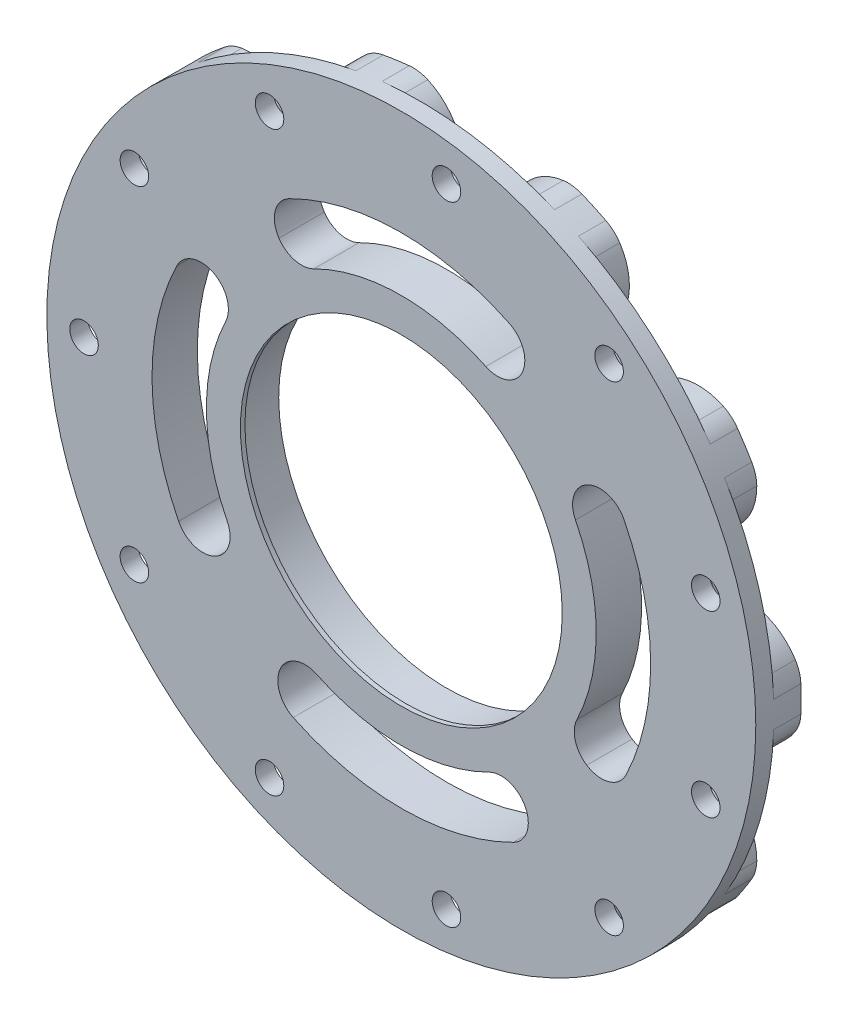
SolidWorks part; units mm, degrees
material "ABS"
ref_plane "Front Plane" through (0, 0, 0) normal (0, 0, 1) x (1, 0, 0)
ref_plane "Top Plane" through (0, 0, 0) normal (0, 1, 0) x (1, 0, 0)
ref_plane "Right Plane" through (0, 0, 0) normal (1, 0, 0) x (0, 0, -1)
ref_plane "Plane1" through (0, 0, 15) normal (0, 0, 1) x (1, 0, 0)
sketch "Sketch1" plane through (0, 0, 15) normal (0, 0, 1) x (1, 0, 0)
  circle A0 centre (0, 0) radius 39.1
  circle A1 centre (0, 0) radius 33 construction
  circle A2 centre (33, 0) radius 2.525
  circle A3 centre (27.7614, -17.8411) radius 2.525
  circle A4 centre (13.7087, -30.0179) radius 2.525
  circle A5 centre (-4.6964, -32.6641) radius 2.525
  circle A6 centre (-21.6104, -24.9397) radius 2.525
  circle A7 centre (-31.6633, -9.2972) radius 2.525
  circle A8 centre (-31.6633, 9.2972) radius 2.525
  circle A9 centre (-21.6104, 24.9397) radius 2.525
  circle A10 centre (-4.6964, 32.6641) radius 2.525
  circle A11 centre (13.7087, 30.0179) radius 2.525
  circle A12 centre (27.7614, 17.8411) radius 2.525
  circle A13 centre (0, 0) radius 16.025
  point P28 (0, 0)
extrude "Boss-Extrude1" add sketch "Sketch1" along normal blind 5
sketch "Sketch2" plane through (0, 0, 15) normal (0, 0, -1) x (-1, 0, 0)
  circle A0 centre (0, 0) radius 18.525
  dimension "D1" = 37.05
extrude "Cut-Extrude1" cut sketch "Sketch2" against normal blind 4.5
sketch "Sketch3" plane through (0, 0, 20) normal (0, 0, 1) x (1, 0, 0)
  circle A1 centre (-4.6964, 32.6641) radius 2.55
  circle A2 centre (13.7087, 30.0179) radius 2.55
  circle A4 centre (27.7614, 17.8411) radius 2.55
  circle A6 centre (33, 0) radius 2.55
  circle A8 centre (27.7614, -17.8411) radius 2.55
  circle A10 centre (13.7087, -30.0179) radius 2.55
  circle A12 centre (-4.6964, -32.6641) radius 2.55
  circle A14 centre (-21.6104, -24.9397) radius 2.55
  circle A16 centre (-31.6633, -9.2972) radius 2.55
  circle A18 centre (-31.6633, 9.2972) radius 2.55
  circle A20 centre (-21.6104, 24.9397) radius 2.55
  point P36 (0, 0)
  dimension "D1" = 5.1
  dimension "D3" = 11
extrude "Boss-Extrude2" add sketch "Sketch3" against normal blind 4
chamfer "Chamfer3" distance 0.5 angle 45 11 edges at (35.525, 0, 15) (30.2864, -17.8411, 15) (16.2337, -30.0179, 15) (-2.1714, -32.6641, 15) (-19.0854, -24.9397, 15) (-29.1383, -9.2972, 15) (-29.1383, 9.2972, 15) (-19.0854, 24.9397, 15) (-2.1714, 32.6641, 15) (16.2337, 30.0179, 15) (30.2864, 17.8411, 15)
sketch "Sketch4" plane through (0, 0, 15) normal (0, 0, -1) x (-1, 0, 0)
  arc A0 (-7.5917, 32.0635) -> (-19.2605, 26.7345) centre (-13.7087, 30.0179) ccw
  circle A1 centre (0, 0) radius 39.1
  arc A2 (10.9483, 31.0779) -> (-1.7492, 32.9035) centre (4.6964, 32.6641) ccw
  arc A3 (26.0123, 20.2253) -> (16.3175, 28.6259) centre (21.6104, 24.9397) ccw
  arc A4 (32.8176, 2.9513) -> (29.2035, 15.2597) centre (31.6633, 9.2972) ccw
  arc A5 (29.2035, -15.2597) -> (32.8176, -2.9513) centre (31.6633, -9.2972) ccw
  arc A6 (16.3175, -28.6259) -> (26.0123, -20.2253) centre (21.6104, -24.9397) ccw
  arc A7 (-1.7492, -32.9035) -> (10.9483, -31.0779) centre (4.6964, -32.6641) ccw
  arc A8 (-19.2605, -26.7345) -> (-7.5917, -32.0635) centre (-13.7087, -30.0179) ccw
  arc A9 (-30.6567, -12.0775) -> (-23.7214, -22.8692) centre (-27.7614, -17.8411) ccw
  arc A10 (-32.3197, 6.414) -> (-32.3197, -6.414) centre (-33, 0) ccw
  arc A11 (-23.7214, 22.8692) -> (-30.6567, 12.0775) centre (-27.7614, 17.8411) ccw
  arc A12 (-32.3197, -6.414) -> (-30.6567, -12.0775) centre (0, 0) ccw
  arc A13 (-30.6567, 12.0775) -> (-32.3197, 6.414) centre (0, 0) ccw
  arc A14 (-19.2605, 26.7345) -> (-23.7214, 22.8692) centre (0, 0) ccw
  arc A15 (-1.7492, 32.9035) -> (-7.5917, 32.0635) centre (0, 0) ccw
  arc A16 (16.3175, 28.6259) -> (10.9483, 31.0779) centre (0, 0) ccw
  arc A17 (29.2035, 15.2597) -> (26.0123, 20.2253) centre (0, 0) ccw
  arc A18 (32.8176, -2.9513) -> (32.8176, 2.9513) centre (0, 0) ccw
  arc A19 (26.0123, -20.2253) -> (29.2035, -15.2597) centre (0, 0) ccw
  arc A20 (10.9483, -31.0779) -> (16.3175, -28.6259) centre (0, 0) ccw
  arc A21 (-7.5917, -32.0635) -> (-1.7492, -32.9035) centre (0, 0) ccw
  arc A22 (-23.7214, -22.8692) -> (-19.2605, -26.7345) centre (0, 0) ccw
  point P28 (0, 0)
  circle M36 centre (0, 0) radius 39.1
  dimension "D1" = 12.9
  dimension "D2" = 78.2
  dimension "D4" = 65.9
  dimension "D3" = 11
extrude "Cut-Extrude2" cut sketch "Sketch4" against normal blind 3 contours A15 A2 A0 M36 | A16 A3 A2 M36 | A17 A4 A3 M36 | A18 A5 A4 M36 | A19 A6 A5 M36 | A20 A7 A6 M36 | A21 A8 A7 M36 | A22 A9 A8 M36 | A12 A10 A9 M36 | A13 A11 A10 M36 | A14 A0 A11 M36 region at (5.1877, 36.0815, 15) region at (23.8713, 27.549, 15) region at (-15.1429, 33.1584, 15) region at (34.9759, 10.2699, 15) region at (-30.6658, 19.7077, 15) region at (34.9759, -10.2699, 15) region at (-36.4525, 0, 15) region at (23.8713, -27.549, 15) region at (5.1877, -36.0815, 15) region at (-30.6658, -19.7077, 15) region at (-15.1429, -33.1584, 15)
fillet "Fillet1" radius 4 22 edges at (-38.0948, -8.809, 16.5) (-36.8099, -13.185, 16.5) (-27.2848, -28.0062, 16.5) (-23.8381, -30.9928, 16.5) (-7.8122, -38.3116, 16.5) (-3.2979, -38.9607, 16.5) (14.1408, -36.4534, 16.5) (18.2894, -34.5588, 16.5) (31.6042, -23.0214, 16.5) (34.0699, -19.1847, 16.5) (39.0334, 2.2804, 16.5) (39.0334, -2.2804, 16.5) (34.0699, 19.1847, 16.5) (31.6042, 23.0214, 16.5) (14.1408, 36.4534, 16.5) (18.2894, 34.5588, 16.5) (-3.2979, 38.9607, 16.5) (-7.8122, 38.3116, 16.5) (-38.0948, 8.809, 16.5) (-36.8099, 13.185, 16.5) (-27.2848, 28.0062, 16.5) (-23.8381, 30.9928, 16.5)
sketch "Sketch5" plane through (0, 0, 20) normal (0, 0, 1) x (1, 0, 0)
  circle A0 centre (0, 0) radius 17.75
  dimension "D1" = 35.5
extrude "Cut-Extrude3" cut sketch "Sketch5" against normal blind 10
chamfer "Chamfer5" [suppressed] distance 0.5 angle 45
sketch "Sketch6" plane through (0, 0, 15) normal (0, 0, -1) x (-1, 0, 0)
  line L0 (0, 0) -> (-27.4458, 18.3229)
  line L1 (0, 0) -> (-27.7614, -17.8411)
  line L2 (0, 0) -> (18.3229, 27.4458)
  line L3 (0, 0) -> (-17.8411, 27.7614)
  line L4 (0, 0) -> (27.4458, -18.3229)
  line L5 (0, 0) -> (27.7614, 17.8411)
  line L6 (0, 0) -> (-18.3229, -27.4458)
  line L7 (0, 0) -> (17.8411, -27.7614)
  line L8 (0, 0) -> (-33, 0) construction
  arc A0 (-18.087, -11.6238) -> (-17.8813, 11.9377) centre (0, 0) cw
  arc A1 (-23.1345, -14.8676) -> (-22.8715, 15.2691) centre (0, 0) cw
  arc A2 (-14.8676, 23.1345) -> (15.2691, 22.8715) centre (0, 0) cw
  arc A3 (-11.6238, 18.087) -> (11.9377, 17.8813) centre (0, 0) cw
  arc A4 (23.1345, 14.8676) -> (22.8715, -15.2691) centre (0, 0) cw
  arc A5 (18.087, 11.6238) -> (17.8813, -11.9377) centre (0, 0) cw
  arc A6 (14.8676, -23.1345) -> (-15.2691, -22.8715) centre (0, 0) cw
  arc A7 (11.6238, -18.087) -> (-11.9377, -17.8813) centre (0, 0) cw
  point P10 (-33, 0)
  point P31 (0, 0)
  dimension "D1" = 21.5
  dimension "D2" = 27.5
  dimension "D4" = 33.727
  dimension "D5" = 32.727
  dimension "D3" = 4
extrude "Cut-Extrude4" cut sketch "Sketch6" against normal through all contours A1 L1 A0 L0 | L3 A3 L2 A2 | L5 A5 L4 A4 | L7 A7 L6 A6 | L8 A0 L0 A1 region at (23.2249, 7.0402, 15) region at (23.3052, -6.843, 15) region at (-0.203, 23.2644, 15) region at (-23.2644, -0.203, 15) region at (0.203, -23.2644, 15)
fillet "Fillet2" radius 3 16 edges at (15.2691, -22.8715, 17.5) (11.9377, -17.8813, 17.5) (-11.6238, -18.087, 17.5) (-23.1345, 14.8676, 17.5) (-18.087, 11.6238, 17.5) (-17.8813, -11.9377, 17.5) (-14.8676, -23.1345, 17.5) (-22.8715, -15.2691, 17.5) (18.087, -11.6238, 17.5) (23.1345, -14.8676, 17.5) (22.8715, 15.2691, 17.5) (17.8813, 11.9377, 17.5) (11.6238, 18.087, 17.5) (14.8676, 23.1345, 17.5) (-15.2691, 22.8715, 17.5) (-11.9377, 17.8813, 17.5)
sketch "Sketch7" plane through (0, 0, 20) normal (0, 0, 1) x (1, 0, 0)
  line L0 (0, 0) -> (-35, 0) construction
  circle A0 centre (-35, 0) radius 1.575
  circle A1 centre (-29.4439, 18.9224) radius 1.575
  circle A2 centre (-14.5395, 31.8371) radius 1.575
  circle A3 centre (4.981, 34.6438) radius 1.575
  circle A4 centre (22.9201, 26.4512) radius 1.575
  circle A5 centre (33.5823, 9.8606) radius 1.575
  circle A6 centre (33.5823, -9.8606) radius 1.575
  circle A7 centre (22.9201, -26.4512) radius 1.575
  circle A8 centre (4.981, -34.6438) radius 1.575
  circle A9 centre (-14.5395, -31.8371) radius 1.575
  circle A10 centre (-29.4439, -18.9224) radius 1.575
  point P4 (0, 0)
  point P5 (0, 0)
  point P26 (0, 0)
  point P28 (0, 0)
  dimension "D2" = 3.15
  dimension "D1" = 35
  dimension "D3" = 11
extrude "Cut-Extrude5" cut sketch "Sketch7" against normal through all
equation "\"RingPinShaft\"= 5.05"
equation "\"CenterBearingOut\"=32.05"
equation "\"OutputBearingOut\"=37.05"
equation "\"RingPostIn\"=5.15"
equation "\"CamBearingOut\"=15.1"
equation "\"DiskOutputShaft\"=10.1"
equation "\"CenterShaft\"=25.2"
equation "\"Eccentricity\"=2"
equation "\"CycCamShaft\"=10.05"
equation "\"m3Thru\"=3.15"
equation "\"m3Insert\"=4.2"
equation "\"D1@Sketch2\"=\"OutputBearingOut\""
equation "\"D2@Sketch7\"=\"m3Thru\""
equation "\"MountingHoleDiam\"=35"
equation "\"D1@Sketch7\"=\"MountingHoleDiam\""
